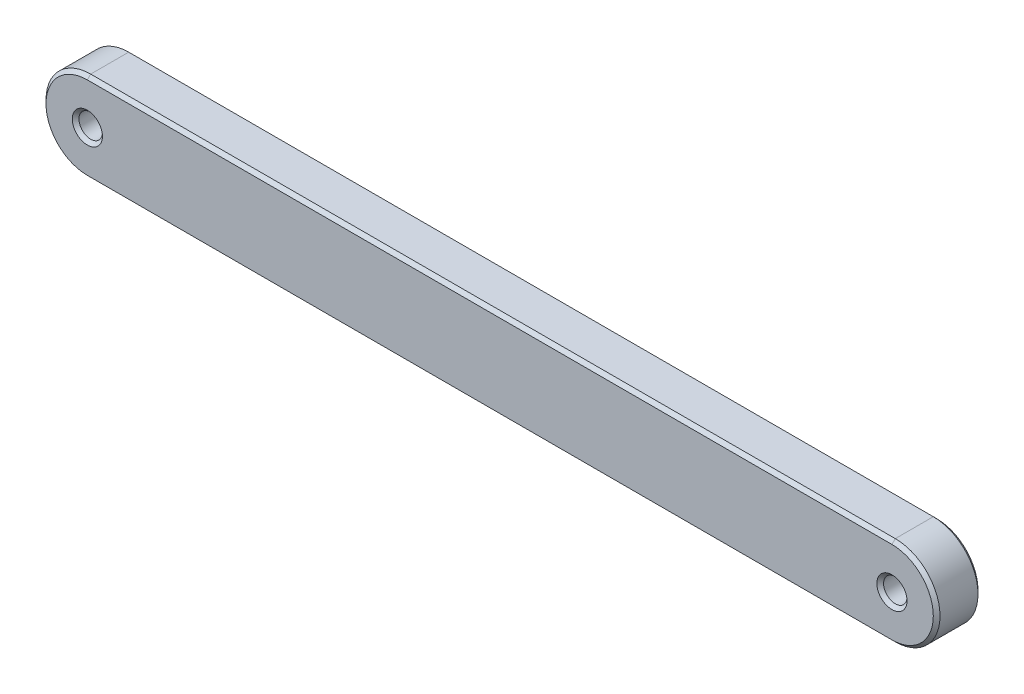
SolidWorks part; units mm, degrees
ref_plane "Front Plane" through (0, 0, 0) normal (0, 0, 1) x (1, 0, 0)
ref_plane "Top Plane" through (0, 0, 0) normal (0, 1, 0) x (1, 0, 0)
ref_plane "Right Plane" through (0, 0, 0) normal (1, 0, 0) x (0, 0, -1)
sketch "Sketch1" plane through (0, 0, 0) normal (0, 0, 1) x (1, 0, 0)
  line L0 (0, 10) -> (180, 10)
  line L1 (180, -10) -> (0, -10)
  circle A0 centre (0, 0) radius 2.625
  circle A1 centre (180, 0) radius 2.625
  arc A2 (0, -10) -> (0, 10) centre (0, 0) cw
  arc A3 (180, -10) -> (180, 10) centre (180, 0) ccw
  point P9 (-10, 0)
  dimension "D2" = 5.25
  dimension "D3" = 10
  dimension "D1" = 180
extrude "Boss-Extrude1" add sketch "Sketch1" along normal blind 10
sketch "Sketch3" plane through (0, 0, 0) normal (0, 0, -1) x (-1, 0, 0)
  circle A0 centre (0, 0) radius 6.5
  point P3 (0, 0)
  point P4 (0, 0)
  point P5 (0, 0)
  dimension "D1" = 13
extrude "Cut-Extrude1" cut sketch "Sketch3" against normal blind 4
chamfer "Chamfer1" distance 0.75 angle 45 13 edges at (2.625, 0, 10) (182.625, 0, 0) (182.625, 0, 10) (90, -10, 10) (190, 0, 10) (-10, 0, 10) (90, 10, 10) (90, -10, 0) (190, 0, 0) (-10, 0, 0) (90, 10, 0) (-6.5, 0, 0) (-2.625, 0, 4)
